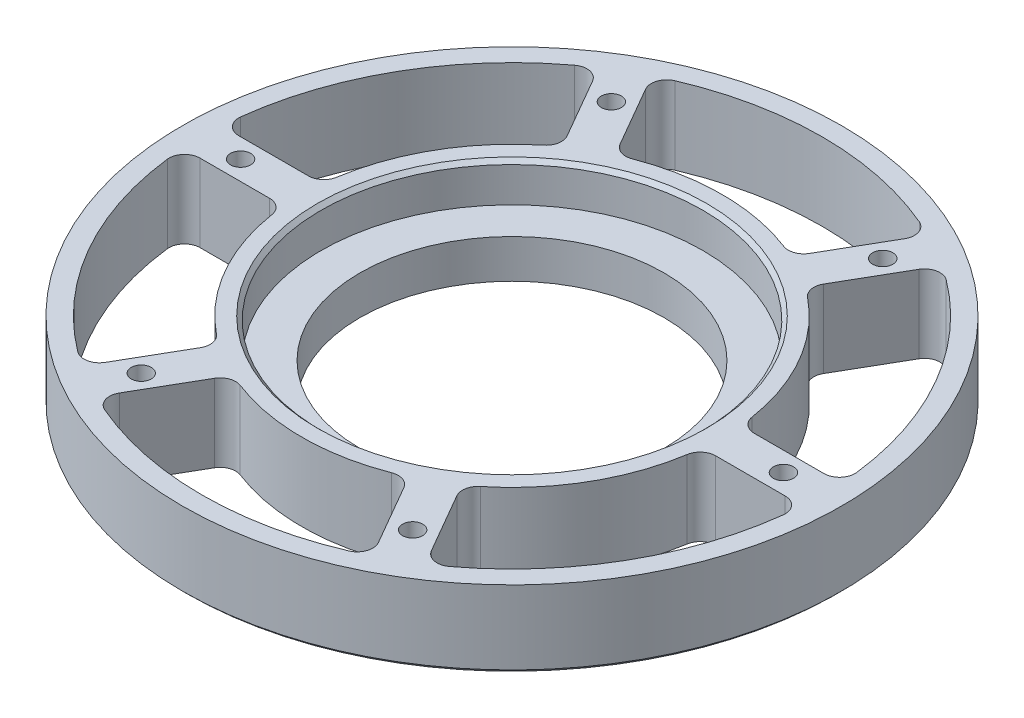
SolidWorks part; units mm, degrees
ref_plane "Front Plane" through (0, 0, 0) normal (0, 0, 1) x (1, 0, 0)
ref_plane "Top Plane" through (0, 0, 0) normal (0, 1, 0) x (1, 0, 0)
ref_plane "Right Plane" through (0, 0, 0) normal (1, 0, 0) x (0, 0, -1)
sketch "Sketch2" plane through (0, 0, 0) normal (1, 0, 0) x (0, 0, -1)
  line L0 (-39.2125, 0) -> (-84.9998, 0)
  line L1 (-84.9998, 0) -> (-84.9998, 20)
  line L2 (-84.9998, 20) -> (-49.2125, 20)
  line L3 (-49.2125, 20) -> (-49.2125, 10)
  line L4 (-49.2125, 10) -> (-39.2125, 10)
  line L5 (-39.2125, 10) -> (-39.2125, 0)
  dimension "D1" = 84.9998
  dimension "D2" = 20
  dimension "D3" = 10
  dimension "D4" = 49.2125
  dimension "D5" = 10
ref_axis "Axis1" through (0, -1, 0) along (0, 1, 0)
revolve "Revolve1" add sketch "Sketch2" angle 360 about axis through (0, -1, 0) along (0, 1, 0)
hole_wizard "#6 (0.204) Diameter Hole1" positions "Sketch6" profile "Sketch7" hole size "#6" standard "ANSI Inch" end condition through all
sketch "Sketch6" plane through (0, 20, 0) normal (0, 1, 0) x (1, 0, 0)
  line L0 (0, 0) -> (-69.8201, 120.932) construction
  line L2 (0, 0) -> (0, 109.0908) construction
  point P0 (-35, 60.6218)
  dimension "D1" = 30
  dimension "D2" = 70
sketch "Sketch7" plane through (-35, 20, -60.6218) normal (1, 0, 0) x (0, 0, 1)
  line L0 (0, 0) -> (0, 20)
  line L1 (0, 20) -> (2.5908, 20)
  line L2 (2.5908, 20) -> (2.5908, 0)
  line L5 (2.5908, 0) -> (0, 0)
  line L11 (0, -6.35) -> (0, 107.95) construction
  dimension "Thru Hole Dia." = 5.1816
  dimension "Thru Hole Depth" = 20
pattern_circular "CirPattern3" count 6 over 360 about axis through (0, -1, 0) along (0, 1, 0) of "#6 (0.204) Diameter Hole1"
sketch "Sketch8" plane through (0, 20, 0) normal (0, 1, 0) x (1, 0, 0)
  line L0 (-35.5916, 71.6464) -> (-22.6606, 49.2493)
  line L1 (35.5916, 71.6464) -> (22.6606, 49.2493)
  line L2 (0, 0) -> (-35, 60.6218) construction
  line L4 (0, 0) -> (0, 93.9995) construction
  arc A0 (-22.6606, 49.2493) -> (22.6606, 49.2493) centre (0, 0) cw
  arc A1 (-35.5916, 71.6464) -> (35.5916, 71.6464) centre (0, 0) cw
  circle A2 centre (0, 0) radius 49.2125 construction
  circle A3 centre (0, 0) radius 84.9998 construction
  dimension "D1" = 5
  dimension "D2" = 5
  dimension "D3" = 5
extrude "Cut-Extrude1" cut sketch "Sketch8" against normal through all
fillet "Fillet1" radius 4 4 edges at (35.5916, 10, -71.6464) (22.6606, 10, -49.2493) (-35.5916, 10, -71.6464) (-22.6606, 10, -49.2493)
pattern_circular "CirPattern4" count 6 over 360 about axis through (0, -1, 0) along (0, 1, 0) of "Cut-Extrude1", "Fillet1"
chamfer "Chamfer1" distance 1 angle 45 1 edges at (0, 20, -49.2125)
chamfer "Chamfer2" distance 1 angle 45 1 edges at (0, 0, -84.9998)
equation "\"TubeDiameter\" = 6.6929in"
equation "\"D1@Sketch2\"=\"TubeDiameter\"/2"
